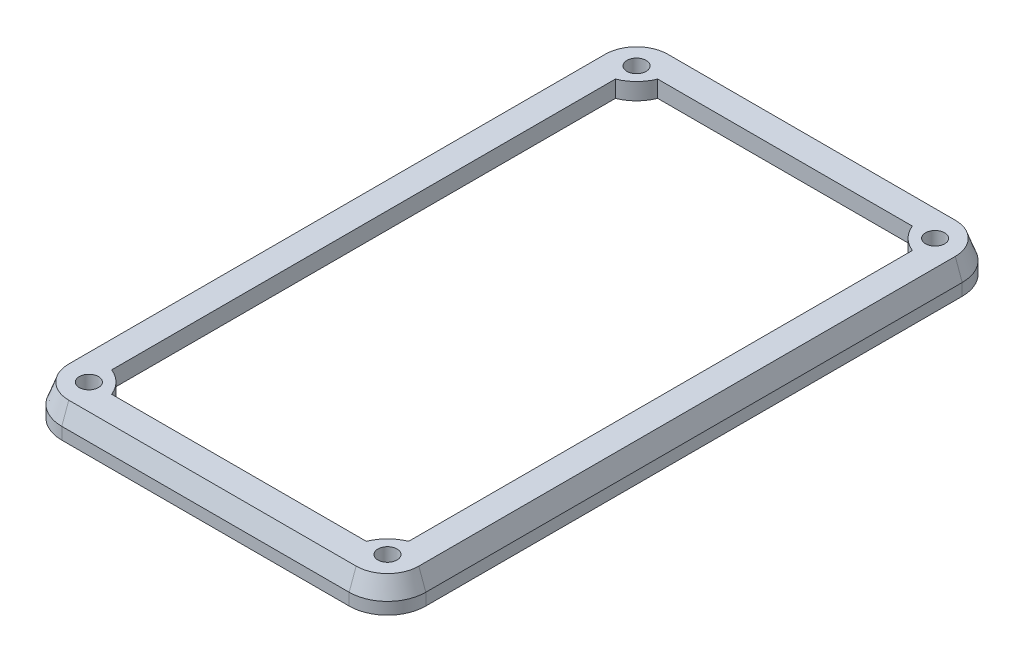
SolidWorks part; units mm, degrees
ref_plane "Front Plane" through (0, 0, 0) normal (0, 0, 1) x (1, 0, 0)
ref_plane "Top Plane" through (0, 0, 0) normal (0, 1, 0) x (1, 0, 0)
ref_plane "Right Plane" through (0, 0, 0) normal (1, 0, 0) x (0, 0, -1)
sketch "Sketch1" plane through (0, 0, 0) normal (0, 1, 0) x (1, 0, 0)
  line L1 (19, -32) -> (-19, -32)
  line L2 (19, -32) -> (19, 32)
  line L3 (19, 32) -> (-19, 32)
  line L4 (-19, -32) -> (-19, 32)
  line L5 (19, -32) -> (-19, 32) construction
  line L6 (19, 32) -> (-19, -32) construction
  line L7 (17, -30) -> (-17, -30)
  line L8 (17, -30) -> (17, 30)
  line L9 (17, 30) -> (-17, 30)
  line L10 (-17, -30) -> (-17, 30)
  line L11 (17, -30) -> (-17, 30) construction
  line L12 (17, 30) -> (-17, -30) construction
  point P0 (0, 0)
  point P6 (0, 0)
  dimension "D1" = 38
  dimension "D2" = 64
  dimension "D3" = 2
  dimension "D4" = 2
extrude "Boss-Extrude1" add sketch "Sketch1" along normal blind 3.25
sketch "Sketch3" plane through (0, 3.25, 0) normal (0, 1, 0) x (1, 0, 0)
  line L0 (-13.2919, -28.5) -> (13.2919, -28.5)
  line L1 (-17, 26) -> (-17, 30)
  line L2 (-17, 30) -> (-13, 30)
  line L4 (0, 27.3879) -> (0, -1.4953) construction
  line L5 (-15.5, 26.2919) -> (-15.5, -26.2919)
  line L6 (-17, 0) -> (17, 0) construction
  line L7 (-13.2919, 28.5) -> (13.2919, 28.5)
  line L9 (-17, 30) -> (-14.1716, 27.1716) construction
  line L11 (-17, 30) -> (-17, 26)
  line L12 (-13, 30) -> (-17, 30)
  line L13 (17, 30) -> (14.1716, 27.1716) construction
  line L14 (13, 30) -> (17, 30)
  line L15 (17, 30) -> (17, 26)
  line L16 (17, 30) -> (13, 30)
  line L17 (17, 26) -> (17, 30)
  line L18 (17, -30) -> (14.1716, -27.1716) construction
  line L19 (-17, -30) -> (-14.1716, -27.1716) construction
  line L20 (17, -26) -> (17, -30)
  line L21 (17, -30) -> (13, -30)
  line L22 (17, -30) -> (17, -26)
  line L23 (13, -30) -> (17, -30)
  line L24 (-13, -30) -> (-17, -30)
  line L25 (-17, -30) -> (-17, -26)
  line L26 (-17, -30) -> (-13, -30)
  line L27 (-17, -26) -> (-17, -30)
  line L28 (-17, 30) -> (-17, -30) construction
  line L29 (17, 30) -> (-17, 30) construction
  line L30 (15.5, 26.2919) -> (15.5, -26.2919)
  circle A1 centre (-15.5858, 28.5858) radius 1
  arc A4 (-17, 26) -> (-13, 30) centre (-17, 30) ccw
  arc A5 (17, 26) -> (13, 30) centre (17, 30) cw
  circle A6 centre (15.5858, 28.5858) radius 1
  circle A7 centre (15.5858, -28.5858) radius 1
  arc A8 (17, -26) -> (13, -30) centre (17, -30) ccw
  arc A9 (-17, -26) -> (-13, -30) centre (-17, -30) cw
  circle A10 centre (-15.5858, -28.5858) radius 1
  point P3 (-17, 0)
  point P11 (0, 30)
  point P23 (0, 0)
  line M105 (17, -30) -> (-17, -30)
  line M106 (-17, -30) -> (-17, 30)
  line M107 (-17, 30) -> (17, 30)
  line M108 (17, 30) -> (17, -30)
  dimension "D2" = 2
  dimension "D1" = 4
  dimension "D3" = 1.5
  dimension "D4" = 1.5
extrude "Boss-Extrude2" add sketch "Sketch3" against normal offset from surface (1.75 mm away) 1.5 contours A4 A1 M106 M107 | A6 A5 M108 M107 | A8 L21 A7 M108 | A9 L24 A10 M106 | A9 L5 A4 M106 | L0 A9 A8 M105 | A8 A5 L30 M108 | L7 A5 A4 M107 region at (-13.1292, 3.25, 29.2467) region at (0, 3.25, 29.2472) region at (14.2116, 3.25, 27.2116) region at (-16.2486, 3.25, 0) region at (16.2486, 3.25, 0) region at (-16.2467, 3.25, -26.1292) region at (14.2116, 3.25, -27.2116) region at (0, 3.25, -29.2472) up to face at (0, 0, 0)
fillet "Fillet1" radius 4 4 edges at (19, 1.625, -32) (-19, 1.625, -32) (19, 1.625, 32) (-19, 1.625, 32)
chamfer "Chamfer1" distance 2 angle 20 8 edges at (19, 3.25, 0) (17.8284, 3.25, 30.8284) (0, 3.25, -32) (0, 3.25, 32) (-17.8284, 3.25, -30.8284) (-17.8284, 3.25, 30.8284) (-19, 3.25, 0) (17.8284, 3.25, -30.8284) first distance on face at (19, 1.625, 0) first distance on face at (17.4142, 1.625, 30.4142) first distance on face at (0, 1.625, -32) first distance on face at (0, 1.625, 32) first distance on face at (-17.4142, 1.625, -30.4142) first distance on face at (-17.4142, 1.625, 30.4142) first distance on face at (-19, 1.625, 0) first distance on face at (17.4142, 1.625, -30.4142)
